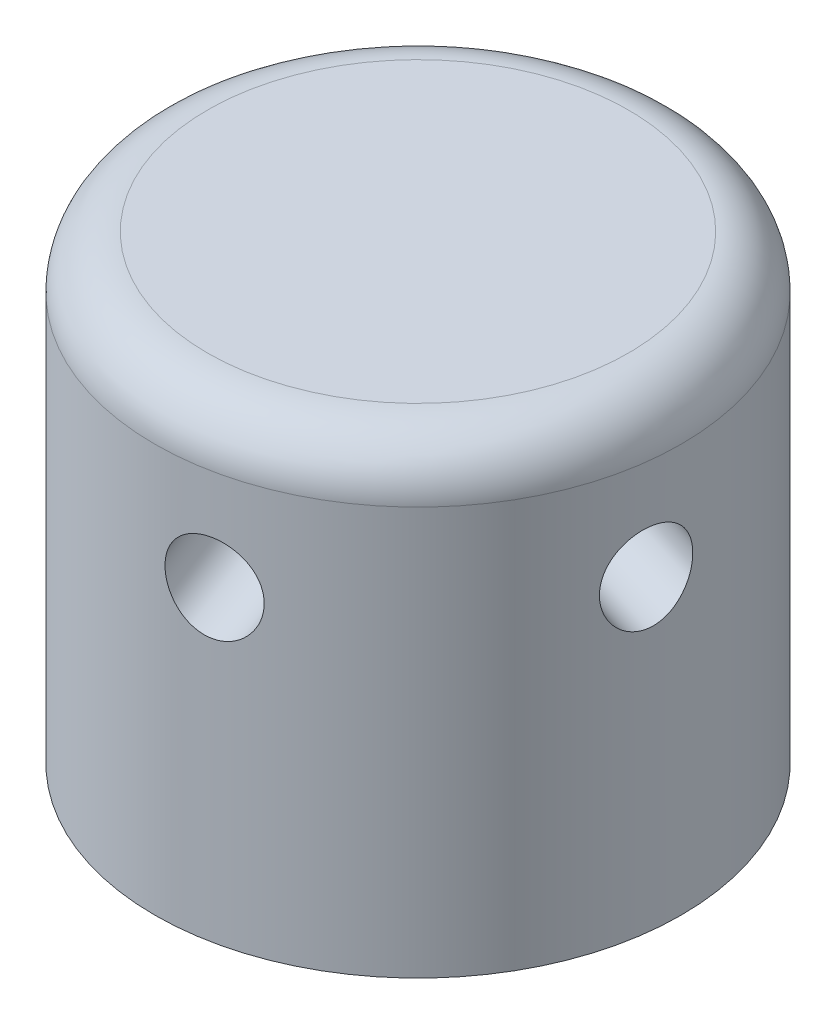
SolidWorks part; units mm, degrees
ref_plane "Front Plane" through (0, 0, 0) normal (0, 0, 1) x (1, 0, 0)
ref_plane "Top Plane" through (0, 0, 0) normal (0, 1, 0) x (1, 0, 0)
ref_plane "Right Plane" through (0, 0, 0) normal (1, 0, 0) x (0, 0, -1)
sketch "Sketch1" plane through (0, 0, 0) normal (0, 1, 0) x (1, 0, 0)
  circle A0 centre (0, 0) radius 10
  dimension "D1" = 20
extrude "Boss-Extrude1" add sketch "Sketch1" along normal blind 3 and the other way blind 6
ref_axis "5hubaxis" through (0, 5.5, 0) along (0, -1, 0)
ref_plane "holeplane" through (-3.3529, -1.0931, 1.8877) normal (0.8382, 0.2733, -0.4719) x (-0.4487, -0.1463, -0.8816)
sketch "Sketch4" plane through (-3.3529, -1.0931, 1.8877) normal (0.8382, 0.2733, -0.4719) x (-0.4487, -0.1463, -0.8816)
  circle A0 centre (0, 0) radius 1.5 construction
  circle A1 centre (0, 0) radius 1.5 construction
  circle A2 centre (0, 0) radius 1.6
  dimension "D1" = 3.2
extrude "hole" cut sketch "Sketch4" against normal through all
pattern_circular "holecir" count 5 over 360 about axis through (0, 5.5, 0) along (0, -1, 0) of "hole"
fillet "Fillet3" radius 2 1 edges at (0, 3, 10)
sketch "Sketch5" plane through (0, -6, 0) normal (0, -1, 0) x (1, 0, 0)
  circle A1 centre (0, 0) radius 10
  circle A2 centre (0, 0) radius 10
  dimension "D1" = 0
extrude "Boss-Extrude2" add sketch "Sketch5" along normal blind 8.5
sketch "Sketch6" plane through (0, -14.5, 0) normal (0, -1, 0) x (1, 0, 0)
  circle A0 centre (0, 0) radius 2
  dimension "D1" = 4
extrude "Cut-Extrude1" cut sketch "Sketch6" against normal blind 11.1
